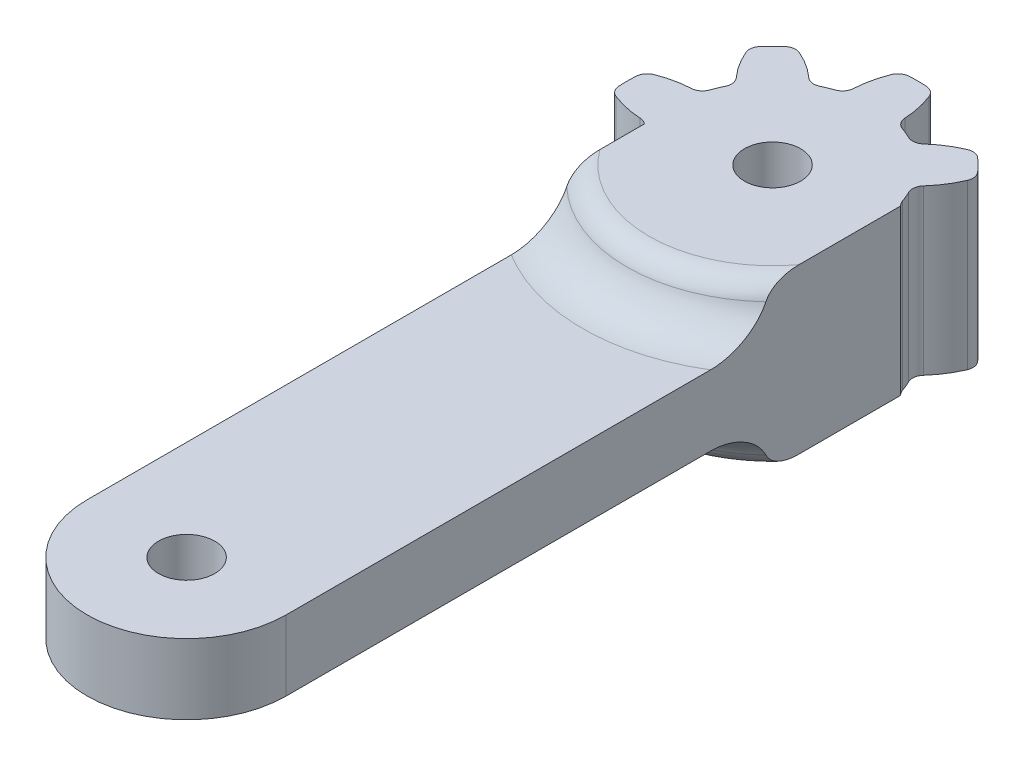
SolidWorks part; units mm, degrees
ref_plane "Front Plane" through (0, 0, 0) normal (0, 0, 1) x (1, 0, 0)
ref_plane "Top Plane" through (0, 0, 0) normal (0, 1, 0) x (1, 0, 0)
ref_plane "Right Plane" through (0, 0, 0) normal (1, 0, 0) x (0, 0, -1)
sketch "Sketch1" plane through (0, 0, 0) normal (0, 1, 0) x (1, 0, 0)
  line L0 (0, -4.35) -> (0, 4.35) construction
  line L3 (-3, 4.35) -> (3, 4.35) construction
  circle A2 centre (0, 0) radius 5.35 construction
  circle A3 centre (0, 10.7) radius 5.35 construction
  circle A4 centre (0, 10.7) radius 6.1 construction
  circle A5 centre (0, 10.7) radius 4.35 construction
  arc A7 (-3.9161, 1.8939) -> (-4.1083, 1.4299) centre (0, 0) ccw
  arc A8 (-0.8055, 5.8758) -> (-1.0948, 4.5554) centre (3, 4.35) ccw
  arc A9 (1.0948, 4.5554) -> (0.8055, 5.8758) centre (-3, 4.35) ccw
  arc A10 (0.3714, 6.1889) -> (-0.3714, 6.1889) centre (0, 0) ccw
  arc A11 (3.9954, 2.447) -> (4.7244, 3.5853) centre (0.9546, 5.1972) ccw
  arc A12 (4.6388, 4.1136) -> (4.1136, 4.6388) centre (0, 0) ccw
  arc A13 (3.5853, 4.7244) -> (2.447, 3.9954) centre (5.1972, 0.9546) ccw
  arc A14 (4.5554, -1.0948) -> (5.8758, -0.8055) centre (4.35, 3) ccw
  arc A15 (6.1889, -0.3714) -> (6.1889, 0.3714) centre (0, 0) ccw
  arc A16 (5.8758, 0.8055) -> (4.5554, 1.0948) centre (4.35, -3) ccw
  arc A17 (2.447, -3.9954) -> (3.5853, -4.7244) centre (5.1972, -0.9546) ccw
  arc A18 (4.1136, -4.6388) -> (4.6388, -4.1136) centre (0, 0) ccw
  arc A19 (4.7244, -3.5853) -> (3.9954, -2.447) centre (0.9546, -5.1972) ccw
  arc A20 (-1.0948, -4.5554) -> (-0.8055, -5.8758) centre (3, -4.35) ccw
  arc A21 (-0.3714, -6.1889) -> (0.3714, -6.1889) centre (0, 0) ccw
  arc A22 (0.8055, -5.8758) -> (1.0948, -4.5554) centre (-3, -4.35) ccw
  arc A23 (-3.9954, -2.447) -> (-4.7244, -3.5853) centre (-0.9546, -5.1972) ccw
  arc A24 (-4.6388, -4.1136) -> (-3.8788, -4.8368) centre (0, 0) ccw
  arc A25 (-3.8788, -4.8368) -> (-2.447, -3.9954) centre (-5.1972, -0.9546) ccw
  arc A26 (-4.5554, 1.0948) -> (-5.8758, 0.8055) centre (-4.35, -3) ccw
  arc A27 (-6.1889, 0.3714) -> (-6.1889, -0.3714) centre (0, 0) ccw
  arc A28 (-5.8758, -0.8055) -> (-4.5554, -1.0948) centre (-4.35, 3) ccw
  arc A29 (-2.447, 3.9954) -> (-3.5853, 4.7244) centre (-5.1972, 0.9546) ccw
  arc A30 (-4.1136, 4.6388) -> (-4.6388, 4.1136) centre (0, 0) ccw
  arc A31 (-4.7244, 3.5853) -> (-3.9954, 2.447) centre (-0.9546, 5.1972) ccw
  arc A32 (-4.1083, -1.4299) -> (-3.9161, -1.8939) centre (0, 0) ccw
  arc A33 (-1.8939, -3.9161) -> (-1.4299, -4.1083) centre (0, 0) ccw
  arc A34 (1.4299, -4.1083) -> (1.8939, -3.9161) centre (0, 0) ccw
  arc A35 (3.9161, -1.8939) -> (4.1083, -1.4299) centre (0, 0) ccw
  arc A36 (4.1083, 1.4299) -> (3.9161, 1.8939) centre (0, 0) ccw
  arc A37 (1.8939, 3.9161) -> (1.4299, 4.1083) centre (0, 0) ccw
  arc A38 (-1.4299, 4.1083) -> (-1.8939, 3.9161) centre (0, 0) ccw
  arc A39 (3.9954, -2.447) -> (3.9161, -1.8939) centre (4.3662, -2.1116) cw
  arc A40 (2.447, -3.9954) -> (1.8939, -3.9161) centre (2.1116, -4.3662) ccw
  arc A41 (-0.8055, -5.8758) -> (-0.3714, -6.1889) centre (-0.3414, -5.6898) ccw
  arc A42 (0.3714, -6.1889) -> (0.8055, -5.8758) centre (0.3414, -5.6898) ccw
  arc A43 (3.5853, -4.7244) -> (4.1136, -4.6388) centre (3.7819, -4.2647) ccw
  arc A44 (4.6388, -4.1136) -> (4.7244, -3.5853) centre (4.2647, -3.7819) ccw
  arc A45 (5.8758, -0.8055) -> (6.1889, -0.3714) centre (5.6898, -0.3414) ccw
  arc A46 (4.5554, -1.0948) -> (4.1083, -1.4299) centre (4.5805, -1.5942) ccw
  arc A47 (3.9954, 2.447) -> (3.9161, 1.8939) centre (4.3662, 2.1116) ccw
  arc A48 (4.5554, 1.0948) -> (4.1083, 1.4299) centre (4.5805, 1.5942) cw
  arc A49 (6.1889, 0.3714) -> (5.8758, 0.8055) centre (5.6898, 0.3414) ccw
  arc A50 (2.447, 3.9954) -> (1.8939, 3.9161) centre (2.1116, 4.3662) cw
  arc A51 (4.7244, 3.5853) -> (4.6388, 4.1136) centre (4.2647, 3.7819) ccw
  arc A52 (4.1136, 4.6388) -> (3.5853, 4.7244) centre (3.7819, 4.2647) ccw
  arc A53 (0.8055, 5.8758) -> (0.3714, 6.1889) centre (0.3414, 5.6898) ccw
  arc A54 (-0.8055, 5.8758) -> (-0.3714, 6.1889) centre (-0.3414, 5.6898) cw
  arc A55 (-1.0948, 4.5554) -> (-1.4299, 4.1083) centre (-1.5942, 4.5805) cw
  arc A56 (-1.0948, -4.5554) -> (-1.4299, -4.1083) centre (-1.5942, -4.5805) ccw
  arc A57 (-2.447, -3.9954) -> (-1.8939, -3.9161) centre (-2.1116, -4.3662) cw
  arc A58 (-4.7244, -3.5853) -> (-4.6388, -4.1136) centre (-4.2647, -3.7819) ccw
  arc A59 (-6.1889, -0.3714) -> (-5.8758, -0.8055) centre (-5.6898, -0.3414) ccw
  arc A60 (-3.9954, -2.447) -> (-3.9161, -1.8939) centre (-4.3662, -2.1116) ccw
  arc A61 (-4.5554, -1.0948) -> (-4.1083, -1.4299) centre (-4.5805, -1.5942) cw
  arc A62 (-5.8758, 0.8055) -> (-6.1889, 0.3714) centre (-5.6898, 0.3414) ccw
  arc A63 (-4.5554, 1.0948) -> (-4.1083, 1.4299) centre (-4.5805, 1.5942) ccw
  arc A64 (-3.9954, 2.447) -> (-3.9161, 1.8939) centre (-4.3662, 2.1116) cw
  arc A65 (-4.6388, 4.1136) -> (-4.7244, 3.5853) centre (-4.2647, 3.7819) ccw
  arc A66 (-3.5853, 4.7244) -> (-4.1136, 4.6388) centre (-3.7819, 4.2647) ccw
  arc A67 (-2.447, 3.9954) -> (-1.8939, 3.9161) centre (-2.1116, 4.3662) ccw
  arc A68 (1.0948, 4.5554) -> (1.4299, 4.1083) centre (1.5942, 4.5805) ccw
  arc A69 (1.0948, -4.5554) -> (1.4299, -4.1083) centre (1.5942, -4.5805) cw
  point P14 (0, 4.35)
  point P92 (-1.0976, 4.2093)
  point P119 (1.0976, 4.2093)
  dimension "D4" = 10.7
  dimension "D5" = 12.2
  dimension "D2" = 8.7
  dimension "D3" = 8.7
  dimension "D6" = 6.2
  dimension "D8" = 4.1
  dimension "D9" = 4.1
  dimension "D11" = 0.5
  dimension "D12" = 0.5
  dimension "D1" = 10.7
  dimension "D7" = 6
  dimension "D10" = 8
extrude "Boss-Extrude1" add sketch "Sketch1" along normal blind 7
sketch "Sketch2" plane through (0, 7, 0) normal (0, 1, 0) x (1, 0, 0)
  line L0 (0, 0) -> (0, -25) construction
  line L1 (4.25, 0) -> (4.25, -25)
  line L2 (-4.25, 0) -> (-4.25, -25)
  arc A0 (4.25, 0) -> (-4.25, 0) centre (0, 0) ccw
  arc A1 (-4.25, -25) -> (4.25, -25) centre (0, -25) ccw
  point P3 (0, -12.5)
  dimension "D1" = 8.5
  dimension "D2" = 25
extrude "Boss-Extrude2" add sketch "Sketch2" against normal blind 7
sketch "Sketch3" plane through (0, 7, 0) normal (0, 1, 0) x (1, 0, 0)
  line L0 (4.25, -4.5141) -> (4.25, 1.4859)
  line L1 (4.25, 1.4859) -> (7.25, 1.4859)
  line L2 (7.25, 1.4859) -> (7.25, -4.5141)
  line L3 (7.25, -4.5141) -> (4.25, -4.5141)
  line L5 (-4.25, -2.7579) -> (-5.25, -2.7579)
  line L6 (-4.25, -2.7579) -> (-4.25, -4.5141)
  line L7 (-4.25, -4.5141) -> (-5.25, -4.5141)
  line L8 (-5.25, -2.7579) -> (-5.25, -4.5141)
  circle A0 centre (0, 0) radius 1.2
  circle A1 centre (0, -25) radius 1.2
  dimension "D1" = 2.4
  dimension "D2" = 2.4
  dimension "D3" = 3
  dimension "D4" = 6
  dimension "D5" = 1
extrude "Cut-Extrude1" cut sketch "Sketch3" against normal blind 7
sketch "Sketch5" plane through (0, 0, 0) normal (0, -1, 0) x (1, 0, 0)
  line L0 (-4.25, 1.219) -> (-4.25, 25) construction
  line L1 (4.25, 25) -> (4.25, -1.219) construction
  line L2 (-4.25, 4.3758) -> (-4.25, 29.25)
  line L3 (-4.25, 29.25) -> (4.25, 29.25)
  line L4 (4.25, 29.25) -> (4.25, 4.3758)
  arc A0 (-4.25, 4.3758) -> (4.25, 4.3758) centre (0, 0) cw
  arc A1 (4.25, 25) -> (-4.25, 25) centre (0, 25) ccw construction
  dimension "D1" = 6.1
extrude "Cut-Extrude2" cut sketch "Sketch5" against normal blind 2
sketch "Sketch6" plane through (0, 7, 0) normal (0, 1, 0) x (1, 0, 0)
  line L0 (-4.25, -1.219) -> (-4.25, -25) construction
  line L1 (4.25, -25) -> (4.25, 1.219) construction
  line L2 (-4.25, -4.3758) -> (-4.25, -29.25)
  line L3 (-4.25, -29.25) -> (4.25, -29.25)
  line L4 (4.25, -29.25) -> (4.25, -4.3758)
  arc A0 (-4.25, -4.3758) -> (4.25, -4.3758) centre (0, 0) ccw
  arc A1 (-4.25, -25) -> (4.25, -25) centre (0, -25) ccw construction
  dimension "D1" = 6.1
extrude "Cut-Extrude3" cut sketch "Sketch6" against normal blind 2
fillet "Fillet1" radius 2 2 edges at (0, 2, 6.1) (0, 5, 6.1)
fillet "Fillet2" radius 1 2 edges at (0, 7, 6.1) (0, 0, 6.1)
